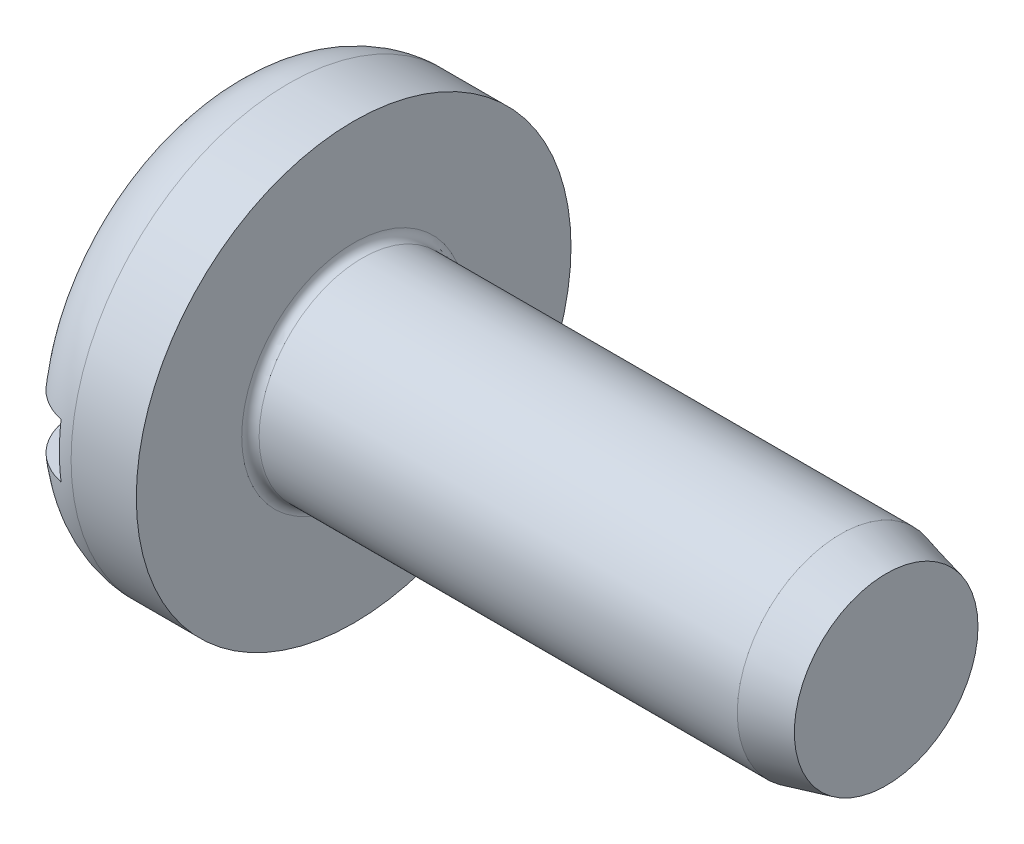
SolidWorks part; units mm, degrees
ref_plane "Front" through (0, 0, 0) normal (0, 0, 1) x (1, 0, 0)
ref_plane "Top" through (0, 0, 0) normal (0, 1, 0) x (1, 0, 0)
ref_plane "Right" through (0, 0, 0) normal (1, 0, 0) x (0, 0, -1)
sketch "Sketch1" plane through (0, 0, 0) normal (0, 0, 1) x (1, 0, 0)
  line L0 (-65.8852, 0) -> (41.8165, 0) construction
  line L1 (30.5, 0) -> (30.5, 4.75)
  line L2 (30.5, 4.75) -> (6, 4.75)
  line L3 (6, 4.75) -> (6, 10)
  line L4 (6, 10) -> (3, 10)
  line L5 (30.5, 0) -> (0, 0)
  line L6 (0, 7) -> (0, 0)
  line L7 (8.1, 7) -> (8.1, -1.5464) construction
  arc A0 (3, 10) -> (0, 7) centre (3, 7) ccw
  dimension "rf" = 3
  dimension "l" = 24.5
  dimension "k" = 6
revolve "Base" add sketch "Sketch1" angle 360 about L0
cosmetic thread "ThreadCosmetic1" [suppressed] parameters "D1"=22.4, "D2"=8.5
sketch "Sketch2" plane through (0, 0, 0) normal (0, 0, 1) x (1, 0, 0)
  line L1 (0, 1.25) -> (2.4, 1.25)
  line L2 (0, 1.25) -> (0, -1.25)
  line L3 (0, -1.25) -> (2.4, -1.25)
  line L4 (2.4, 1.25) -> (2.4, -1.25)
  line L5 (0, 7) -> (0, -7) construction
  line L6 (1.1738, 0) -> (-4.2219, 0) construction
  dimension "n" = 2.5
  dimension "t" = 2.4
extrude "Slot" cut sketch "Sketch2" against normal through all and the other way through all
fillet "Fillet1" radius 0.4 1 edges at (6, 0, 4.75)
sketch "Sketch3" plane through (0, 0, 0) normal (0, 0, 1) x (1, 0, 0)
  line L0 (1.3282, 0) -> (-13.6388, 0) construction
  line L2 (26.3, -4.75) -> (28.4, -4.75)
  line L3 (28.4, -4.75) -> (30.5, -4.225)
  line L6 (26.3, -4.75) -> (26.3, -5.25)
  line L7 (26.3, -5.25) -> (30.5, -5.25)
  line L8 (30.5, -5.25) -> (30.5, -4.225)
  line L9 (30.5, -4.75) -> (30.5, 4.75) construction
  line L10 (6.4, -4.75) -> (30.5, -4.75) construction
  point P15 (28.4, -4.75)
  dimension "D2" = 2.1
  dimension "D4" = 0.5
  dimension "D3" = 0.525
revolve "Cut-Revolve1" cut sketch "Sketch3" angle 360 about L0
sketch "Sketch4" plane through (0, 0, 0) normal (0, 0, 1) x (1, 0, 0)
  line L0 (33.2407, 0) -> (9.9121, 0) construction
  line L2 (30.5, -4.75) -> (30.5, 4.75) construction
  line L3 (30.5, 0) -> (22.5, -4.75) construction
  line L6 (30.5, 0) -> (31, 0)
  line L7 (22.5, -4.75) -> (30.5, -4.75)
  line L8 (31, 0) -> (31, -4.75)
  line L9 (31, -4.75) -> (30.5, -4.75)
  arc A0 (30.5, 0) -> (22.5, -4.75) centre (10.3363, 24.8481) cw
  dimension "D1" = 32
  dimension "D3" = 9.5
  dimension "D2" = 0.5
revolve "Cut-Revolve6" [suppressed] cut sketch "Sketch4" angle 360 about L0
sketch "Sketch5" plane through (0, 0, 0) normal (0, 0, 1) x (1, 0, 0)
  line L0 (7.85, 5.25) -> (8.35, 5.25)
  line L1 (8.35, 5.25) -> (8.35, 4.75)
  line L2 (8.35, 4.75) -> (8.1, 4.317)
  line L3 (8.1, 4.317) -> (7.85, 4.75)
  line L4 (7.85, 4.75) -> (7.85, 5.25)
  line L5 (0, 0) -> (1.9875, 0) construction
  line L6 (6, -10) -> (6, 10) construction
  dimension "D1" = 9.5
  dimension "D2" = 0.5
  dimension "D3" = 2.1
revolve "Cut-Revolve10" [suppressed] cut sketch "Sketch5" angle 360 about L5
pattern_linear "LPattern10" [suppressed] count 37 spacing 0.6 along (1, 0, 0) of bodies 105
equation "\"D3@Sketch3\" = \"yf@Sketch3\" / 8"
equation "\"D2@ThreadCosmetic1\" = \"st@Sketch1\" - 1"
equation "\"D1@Sketch4\" = \"yc@Sketch4\" * 4"
equation "\"D3@Sketch4\" = \"st@Sketch1\""
equation "\"D2@Sketch3\" = \"yf@Sketch3\" / 2"
equation "\"D1@ThreadCosmetic1\" = \"l@Sketch1\" - \"a@Sketch1\""
equation "\"D1@Sketch5\" = \"st@Sketch1\""
equation "\"D2@Sketch5\" =  ( \"st@Sketch1\" - \"D2@ThreadCosmetic1\" )  / 2"
equation "\"D3@Sketch5\" = \"a@Sketch1\""
equation "\"D3@LPattern10\" =  ( \"st@Sketch1\" - \"D2@ThreadCosmetic1\" )  / 2 * 1.2"
equation "\"D1@LPattern10\" = \"D1@ThreadCosmetic1\" / \"D3@LPattern10\""
